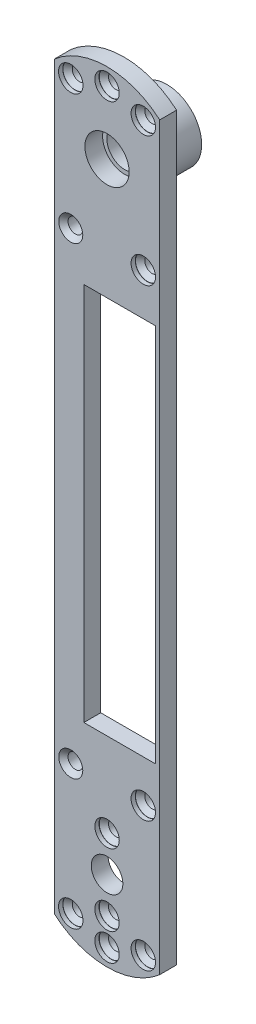
SolidWorks part; units mm, degrees
ref_plane "Front Plane" through (0, 0, 0) normal (0, 0, 1) x (1, 0, 0)
ref_plane "Top Plane" through (0, 0, 0) normal (0, 1, 0) x (1, 0, 0)
ref_plane "Right Plane" through (0, 0, 0) normal (1, 0, 0) x (0, 0, -1)
sketch "Sketch1" plane through (0, 0, 0) normal (0, 0, 1) x (1, 0, 0)
  line L0 (18.375, 147) -> (18.375, 0)
  line L1 (43.375, 147) -> (43.375, 0)
  circle A0 centre (30.875, 8.5) radius 1.75
  circle A1 centre (30.875, 0) radius 12.5 construction
  circle A2 centre (30.875, 0) radius 12.5
  circle A3 centre (30.875, -8.5) radius 1.75
  circle A4 centre (30.875, 0) radius 3.75
  circle A5 centre (30.875, -8.5) radius 1.25 construction
  circle A6 centre (30.875, 147) radius 12.5
  circle A7 centre (30.875, 147) radius 5.25
  circle A8 centre (30.875, 147) radius 5 construction
  circle A11 centre (30.875, 8.5) radius 1.25 construction
  circle A12 centre (30.875, 147) radius 5 construction
  dimension "D2" = 3.5
  dimension "D3" = 7.5
  dimension "D1" = 0.25
extrude "Boss-Extrude1" add sketch "Sketch1" along normal blind 4 contours A6 | A6 L0 A2 L1 | A2 A4 A3 A0 region at (30.875, 73.5, 0) region at (30.875, 159.1464, 0) region at (30.875, 12.1464, 0)
sketch "Sketch2" plane through (0, 0, 0) normal (0, 0, 1) x (1, 0, 0)
  circle A0 centre (30.875, 147) radius 5.25
  circle A1 centre (30.875, 147) radius 5.25 construction
  circle A2 centre (30.875, 147) radius 8.25
  dimension "D1" = 3
extrude "Boss-Extrude2" add sketch "Sketch2" against normal blind 0.2
sketch "Sketch3" plane through (0, 0, -0.2) normal (0, 0, -1) x (-1, 0, 0)
  circle A0 centre (-30.875, 147) radius 8.25 construction
  circle A1 centre (-30.875, 147) radius 8.25
  circle A2 centre (-30.875, 147) radius 4.25
  circle A3 centre (-30.875, 147) radius 5.25 construction
  dimension "D1" = 1
extrude "Boss-Extrude3" add sketch "Sketch3" along normal blind 5.8
sketch "Sketch4" plane through (0, 0, -6) normal (0, 0, -1) x (-1, 0, 0)
  circle A0 centre (-30.875, 147) radius 8.25 construction
  circle A1 centre (-30.875, 147) radius 8.25
  circle A2 centre (-30.875, 147) radius 5.25
  circle A3 centre (-30.875, 147) radius 5.25 construction
extrude "Boss-Extrude4" add sketch "Sketch4" along normal blind 4.2
sketch "Sketch9" plane through (0, 0, 0) normal (0, 0, -1) x (-1, 0, 0)
  line L0 (-43.375, 161.3091) -> (-43.375, -14.3091)
  line L1 (-43.375, 147) -> (-43.375, 0) construction
  line L2 (-18.375, 161.3091) -> (-18.375, -14.3091)
  line L3 (-18.375, 147) -> (-18.375, 0) construction
  circle A0 centre (-30.875, 147) radius 19
  circle A1 centre (-30.875, 0) radius 19
  arc A2 (-18.375, 147) -> (-43.375, 147) centre (-30.875, 147) ccw construction
  arc M15 (-18.375, 147) -> (-43.375, 147) centre (-30.875, 147) ccw
  arc M17 (-43.375, 0) -> (-18.375, 0) centre (-30.875, 0) ccw
  dimension "D1" = 6.5
extrude "Boss-Extrude5" add sketch "Sketch9" against normal up to surface (4 mm away) contours L2 A0 L0 M15 | L0 A1 L2 M17 region at (30.875, 160.2864, 0) region at (30.875, -13.2864, 0) up to face at (36.125, 147, 4)
sketch "Sketch10" plane through (0, 0, 4) normal (0, 0, 1) x (1, 0, 0)
  line L0 (30.875, 166) -> (30.875, -19) construction
  line L1 (30.875, 147) -> (19.977, 162.5639) construction
  line L2 (39.4786, 159.2873) -> (39.4786, -12.2873) construction
  line L3 (18.375, 73.5) -> (43.375, 73.5) construction
  line L4 (18.375, 161.3091) -> (18.375, -14.3091) construction
  line L5 (43.375, 161.3091) -> (43.375, -14.3091) construction
  circle A0 centre (30.875, 147) radius 15
  arc A1 (43.375, 161.3091) -> (18.375, 161.3091) centre (30.875, 147) ccw construction
  arc A2 (18.375, -14.3091) -> (43.375, -14.3091) centre (30.875, 0) ccw construction
  circle A3 centre (30.875, 162) radius 1.75
  circle A4 centre (22.2714, 159.2873) radius 1.75
  circle A5 centre (39.4786, 159.2873) radius 1.75
  circle A6 centre (39.4786, -12.2873) radius 1.75
  circle A7 centre (30.875, -15) radius 1.75
  circle A8 centre (22.2714, -12.2873) radius 1.75
  circle A9 centre (39.4786, 128.5) radius 1.75
  circle A10 centre (39.4786, 18.5) radius 1.75
  circle A11 centre (22.2714, 18.5) radius 1.75
  circle A12 centre (22.2714, 128.5) radius 1.75
  dimension "D1" = 4
  dimension "D2" = 3.5
  dimension "D3" = 35
  dimension "D4" = 110
extrude "Cut-Extrude4" cut sketch "Sketch10" against normal up to next contours A0 A4 | A0 A4 | A0 A3 | A0 A3 | A5 A0 | A5 A0 | A8 | A7 | A6 | A9 | A10 | A12 | A11 region at (39.0423, 158.6641, 4) region at (39.8939, 159.8804, 4) region at (21.8561, 159.8804, 4) region at (22.7077, 158.6641, 4) region at (30.875, 161.2392, 4) region at (30.875, 162.724, 4) region at (39.4786, -12.2873, 4) region at (30.875, -15, 4) region at (22.2714, -12.2873, 4) region at (39.4786, 128.5, 4) region at (39.4786, 18.5, 4) region at (22.2714, 18.5, 4) region at (22.2714, 128.5, 4)
sketch "Sketch8" plane through (0, 0, 4) normal (0, 0, 1) x (1, 0, 0)
  circle A0 centre (30.875, 8.5) radius 2.9
  circle A1 centre (30.875, -8.5) radius 2.9
  circle A2 centre (22.2714, -12.2873) radius 2.9
  circle A3 centre (30.875, -15) radius 2.9
  circle A4 centre (39.4786, -12.2873) radius 2.9
  circle A5 centre (22.2714, 159.2873) radius 2.9
  circle A6 centre (30.875, 162) radius 2.9
  circle A7 centre (39.4786, 159.2873) radius 2.9
  circle A8 centre (39.4786, 159.2873) radius 1.75 construction
  circle A9 centre (39.4786, -12.2873) radius 1.75 construction
  circle A10 centre (22.2714, -12.2873) radius 1.75 construction
  circle A11 centre (30.875, -15) radius 1.75 construction
  circle A12 centre (39.4786, 128.5) radius 2.9
  circle A13 centre (39.4786, 18.5) radius 2.9
  circle M10 centre (30.875, -8.5) radius 1.75
  circle M11 centre (30.875, 8.5) radius 1.75
  circle M59 centre (39.4786, 18.5) radius 1.75
  circle M60 centre (39.4786, 128.5) radius 1.75
  dimension "D1" = 5.8
extrude "Cut-Extrude3" cut sketch "Sketch8" against normal blind 1 contours A5 | A6 | A7 | A2 | A3 | A4 | A0 M11 | A1 M10 | A12 M60 | A13 M59 region at (28.057, 8.5, 4) region at (28.057, -8.5, 4) region at (22.2714, -12.2873, 4) region at (30.875, -15, 4) region at (39.4786, -12.2873, 4) region at (22.2714, 159.2873, 4) region at (30.875, 162, 4) region at (39.4786, 159.2873, 4) region at (36.6607, 128.5, 4) region at (36.6607, 18.5, 4)
chamfer "Chamfer1" distance 1.1 angle 45 12 edges at (41.2286, -12.2873, 3) (32.625, -15, 3) (24.0214, -12.2873, 3) (41.2286, 159.2873, 3) (32.625, 162, 3) (24.0214, 159.2873, 3) (32.625, -8.5, 3) (32.625, 8.5, 3) (41.2286, 18.5, 3) (41.2286, 128.5, 3) (24.0214, 128.5, 4) (24.0214, 18.5, 4)
fillet "Fillet2" radius 2 1 edges at (39.125, 147, 0)
sketch "Sketch11" plane through (0, 0, 0) normal (0, 0, 1) x (1, 0, 0)
  line L0 (43.375, 161.3091) -> (43.375, -14.3091) construction
  line L1 (25.375, 28.5) -> (42.375, 28.5)
  line L2 (25.375, 28.5) -> (25.375, 118.5)
  line L3 (25.375, 118.5) -> (42.375, 118.5)
  line L4 (42.375, 28.5) -> (42.375, 118.5)
  line L5 (18.375, 73.5) -> (43.375, 73.5) construction
  line L6 (18.375, 161.3091) -> (18.375, -14.3091) construction
  line L7 (25.375, 73.5) -> (42.375, 73.5) construction
  dimension "D1" = 1
  dimension "D2" = 90
  dimension "D3" = 17
extrude "Cut-Extrude5" cut sketch "Sketch11" along normal up to next
